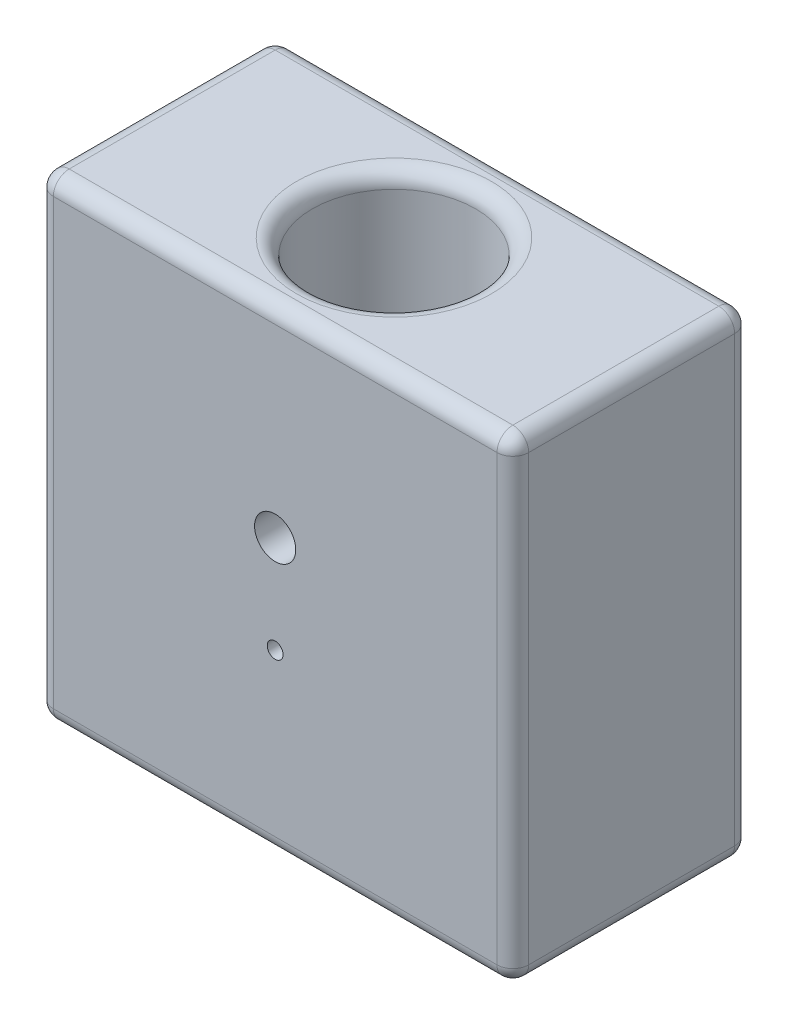
SolidWorks part; units mm, degrees
note: The reader was unsure of these and kept them because the rebuilt part matched: shared geometry of "Sketch2<3>".
ref_plane "Front Plane" through (0, 0, 0) normal (0, 0, 1) x (1, 0, 0)
ref_plane "Top Plane" through (0, 0, 0) normal (0, 1, 0) x (1, 0, 0)
ref_plane "Right Plane" through (0, 0, 0) normal (1, 0, 0) x (0, 0, -1)
sketch "Sketch1" plane through (0, 0, 0) normal (0, 1, 0) x (1, 0, 0)
  line L1 (-19.05, -9.525) -> (19.05, -9.525)
  line L2 (-19.05, -9.525) -> (-19.05, 9.525)
  line L3 (-19.05, 9.525) -> (19.05, 9.525)
  line L4 (19.05, -9.525) -> (19.05, 9.525)
  line L5 (-19.05, -9.525) -> (19.05, 9.525) construction
  line L6 (-19.05, 9.525) -> (19.05, -9.525) construction
  point P0 (0, 0)
  dimension "D1" = 38.1
  dimension "D2" = 19.05
extrude "Boss-Extrude1" add sketch "Sketch1" along normal blind 12.7
sketch "Sketch2" plane through (0, 12.7, 0) normal (0, 1, 0) x (1, 0, 0)
  circle A0 centre (0, 0) radius 6.5405
  circle A1 centre (0, 0) radius 5.461
  dimension "D1" = 13.081
  dimension "D2" = 10.922
extrude "Boss-Extrude2" add sketch "Sketch2" along normal blind 25.4
extrude "Boss-Extrude3" add sketch "Sketch2<3>" along normal blind 15.24
sketch "Sketch2<3>" plane through (0, 12.7, 0) normal (0, 1, 0) x (1, 0, 0) same geometry as "Sketch2"
sketch "Sketch3" plane through (0, 0, -9.525) normal (0, 0, -1) x (-1, 0, 0)
  line L0 (0, 14.224) -> (0, 12.7) construction
  line L1 (6.5405, 12.7) -> (-6.5405, 12.7) construction
  line L2 (6.5405, 12.7) -> (-6.5405, 12.7)
  line L3 (0, 22.0218) -> (0, 12.7) construction
  circle A0 centre (0, 14.224) radius 0.635
  circle A1 centre (0, 22.0218) radius 1.651
  dimension "D2" = 1.27
  dimension "D1" = 9.3218
  dimension "D4" = 3.302
  dimension "D3" = 1.524
extrude "Cut-Extrude1" cut sketch "Sketch3" against normal through all
sketch "Sketch4" plane through (0, 0, -9.525) normal (0, 0, -1) x (-1, 0, 0)
  line L0 (-5.08, 14.224) -> (-5.08, 0)
  line L1 (-19.05, 0) -> (19.05, 0) construction
  line L2 (5.08, 14.224) -> (5.08, 0)
  line L3 (5.08, 0) -> (-5.08, 0)
  line L4 (-5.08, 22.0218) -> (-5.08, 14.224)
  line L5 (5.08, 22.0218) -> (5.08, 14.224)
  circle A0 centre (0, 14.224) radius 0.635 construction
  circle A1 centre (0, 14.224) radius 0.635 construction
  circle A2 centre (0, 14.224) radius 5.08
  circle A3 centre (0, 22.0218) radius 1.651 construction
  circle A4 centre (0, 22.0218) radius 1.651 construction
  circle A5 centre (0, 22.0218) radius 5.08
  circle M3 centre (0, 14.224) radius 0.635
  line M4 (-19.05, 0) -> (19.05, 0)
  circle M13 centre (0, 22.0218) radius 1.651
  dimension "D1" = 10.16
extrude "Boss-Extrude4" add sketch "Sketch4" along normal blind 6.35 contours A2 M3 | A2 L0 L2 M4 | A5 L4 A2 | A2 A5 | A5 A2 M13 | A5 A2 L5
fillet "Fillet3" radius 1.27 23 edges at (-12.065, 0, -9.525) (12.065, 0, -9.525) (0, 0, 9.525) (19.05, 19.05, 9.525) (19.05, 19.05, -9.525) (19.05, 0, 0) (-19.05, 19.05, -9.525) (-19.05, 19.05, 9.525) (-19.05, 0, 0) (0, 38.1, 9.525) (0, 38.1, -9.525) (19.05, 38.1, 0) (-19.05, 38.1, 0) (5.08, 0, -12.7) (0, 27.1018, -15.875) (0, 0, -15.875) (-5.08, 0, -12.7) (-5.08, 11.0109, -15.875) (-5.08, 11.0109, -9.525) (5.08, 11.0109, -15.875) (5.08, 11.0109, -9.525) (0, 38.1, 6.5405) (0, 27.1018, -9.525)
fillet "Fillet4" radius 1.27 1 edges at (0, 27.94, 5.461)
chamfer "Chamfer1" distance 0.381 angle 45 1 edges at (-0.635, 14.224, -15.875)
chamfer "Chamfer2" distance 0.508 angle 45 1 edges at (-1.651, 22.0218, -15.875)
